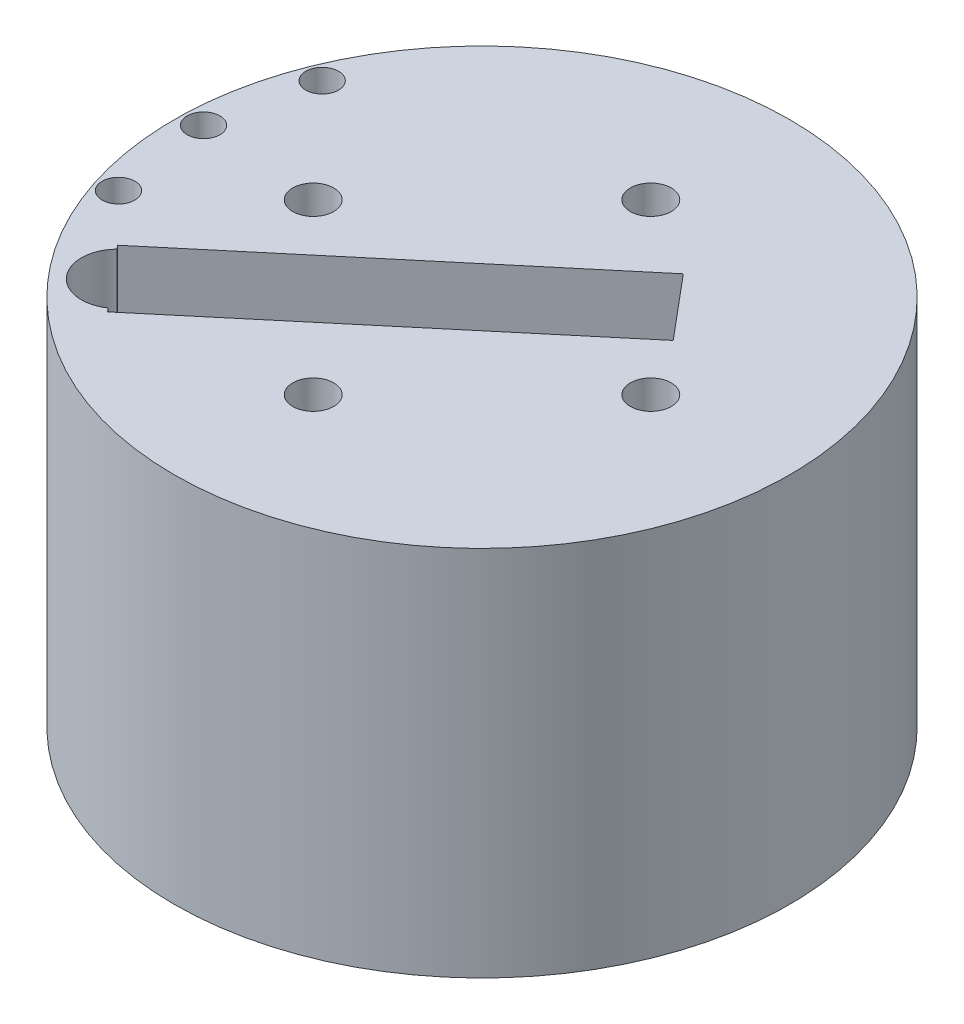
SolidWorks part; units mm, degrees
ref_plane "Front Plane" through (0, 0, 0) normal (0, 0, 1) x (1, 0, 0)
ref_plane "Top Plane" through (0, 0, 0) normal (0, 1, 0) x (1, 0, 0)
ref_plane "Right Plane" through (0, 0, 0) normal (1, 0, 0) x (0, 0, -1)
sketch "Sketch2" plane through (0, 0, 0) normal (0, 1, 0) x (1, 0, 0)
  circle A0 centre (0, 0) radius 47.6885
  dimension "D1" = 95.377
extrude "Boss-Extrude1" add sketch "Sketch2" along normal blind 57.658
sketch "Sketch4" plane through (0, 57.658, 0) normal (0, 1, 0) x (1, 0, 0)
  circle A1 centre (-26.162, 0) radius 3.175
  circle A2 centre (26.162, 0) radius 3.175
  circle A3 centre (0, 26.162) radius 3.175
  circle A4 centre (0, -26.162) radius 3.175
sketch "Sketch5" plane through (0, 57.658, 0) normal (0, 1, 0) x (1, 0, 0)
  line L0 (0, 0) -> (-44.6487, 1.4926)
  line L1 (0, 0) -> (-41.4455, 16.6734)
  line L2 (0, 0) -> (-42.4665, -13.8681)
  line L4 (0, 0) -> (-30.6943, -25.7555)
  circle A1 centre (-41.4455, 16.6734) radius 2.54
  circle A2 centre (0, 0) radius 44.6736
  circle A3 centre (-44.6487, 1.4926) radius 2.54
  circle A4 centre (-42.4665, -13.8681) radius 2.54
  circle A9 centre (-30.6943, -25.7555) radius 5.6388
  dimension "D3" = 11.2776
  dimension "D5" = 89.3472
  dimension "D1" = 20
  dimension "D2" = 20
  dimension "D6" = 21.915
  dimension "D4" = 40.0685
extrude "Cut-Extrude2" cut sketch "Sketch5" against normal through all contours A9 | A1 | A3 | A4
extrude "Cut-Extrude3" cut sketch "Sketch4" against normal through all
sketch "Sketch6" plane through (0, 57.658, 0) normal (0, 1, 0) x (1, 0, 0)
  line L1 (-27.0503, -30.9873) -> (20.6206, 9.0134)
  line L2 (-27.0503, -30.9873) -> (-35.2137, -21.2585)
  line L3 (-35.2137, -21.2585) -> (12.4572, 18.7422)
  line L4 (20.6206, 9.0134) -> (12.4572, 18.7422)
  dimension "D1" = 62.23
  dimension "D2" = 12.7
  dimension "D3" = 6.35
  dimension "D4" = 21.59
  dimension "D5" = 90
  dimension "D6" = 90
  dimension "D7" = 90
extrude "Cut-Extrude4" cut sketch "Sketch6" against normal blind 43.18
sketch "Sketch11" plane through (0, 0, 0) normal (0, -1, 0) x (1, 0, 0)
  circle A0 centre (0, 26.162) radius 6.35
  circle A1 centre (26.162, 0) radius 6.35
  circle A2 centre (0, -26.162) radius 6.35
  circle A3 centre (-26.162, 0) radius 6.35
  dimension "D1" = 12.7
  dimension "D2" = 12.7
  dimension "D3" = 12.7
  dimension "D4" = 12.7
extrude "Cut-Extrude7" cut sketch "Sketch11" against normal blind 7.62
sketch "Sketch14" plane through (0, 0, 0) normal (0, -1, 0) x (1, 0, 0)
  circle A0 centre (1.3569, -14.949) radius 2.067
  circle A1 centre (4.5237, 8.9723) radius 2.067
extrude "Cut-Extrude8" cut sketch "Sketch14" against normal blind 19.05
sketch "Sketch15" plane through (0, 0, 0) normal (0, -1, 0) x (1, 0, 0)
  line L0 (47.6885, 0) -> (-47.6885, 0)
  line L1 (0, -47.6885) -> (0, 47.6885)
  circle A0 centre (0, 0) radius 47.6885 construction
  circle A1 centre (1.3569, -14.949) radius 2.067 construction
  circle A2 centre (1.3569, -14.949) radius 2.067 construction
  circle A3 centre (4.5237, 8.9723) radius 2.067 construction
  point P9 (0, 0)
  dimension "D1" = 1.3569
  dimension "D2" = 14.949
  dimension "D3" = 8.9723
  dimension "D4" = 4.5237
equation "\"D4@Sketch5\"=(3.755/2)-(0.5/2)-0.05"
equation "\"D1@Sketch6\"=2.10 + (0.85-0.5)"
